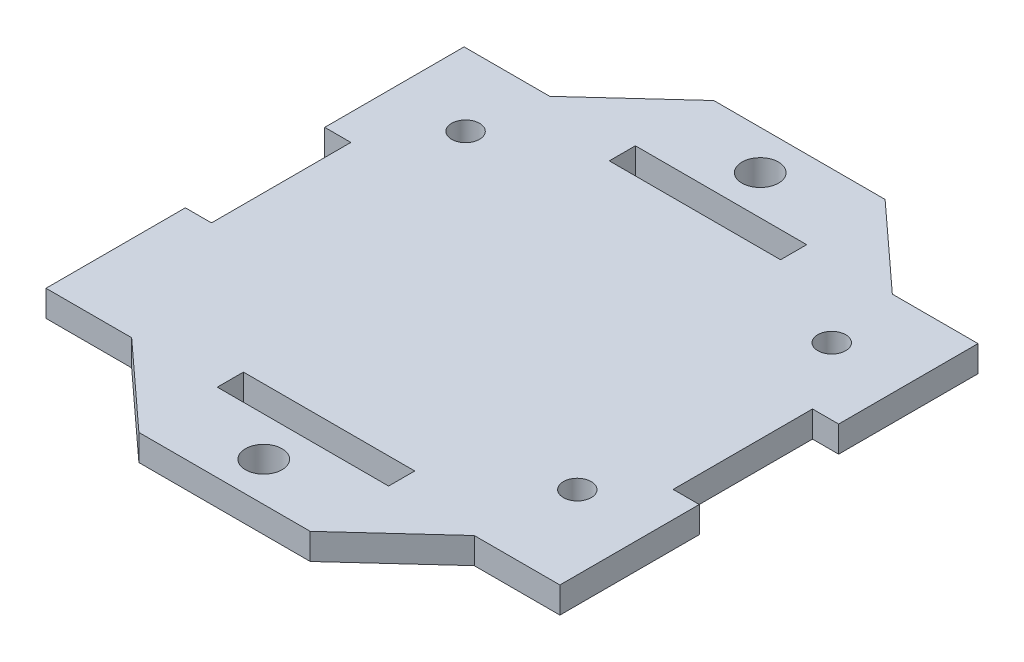
SolidWorks part; units mm, degrees
ref_plane "Front Plane" through (0, 0, 0) normal (0, 0, 1) x (1, 0, 0)
ref_plane "Top Plane" through (0, 0, 0) normal (0, 1, 0) x (1, 0, 0)
ref_plane "Right Plane" through (0, 0, 0) normal (1, 0, 0) x (0, 0, -1)
sketch "Sketch1" plane through (0, 0, 0) normal (0, 1, 0) x (1, 0, 0)
  line L0 (-29.5, 24) -> (-29.5, 8)
  line L1 (-25, -19.5) -> (25, -19.5) construction
  line L2 (-25, -19.5) -> (-25, 19.5) construction
  line L3 (-25, 19.5) -> (25, 19.5) construction
  line L4 (25, -19.5) -> (25, 19.5) construction
  line L5 (-25, -19.5) -> (25, 19.5) construction
  line L6 (-25, 19.5) -> (25, -19.5) construction
  line L11 (-29.5, 8) -> (-26.5, 8)
  line L12 (-26.5, 8) -> (-26.5, -8)
  line L13 (-26.5, -8) -> (-29.5, -8)
  line L14 (-29.5, -8) -> (-29.5, -24)
  line L15 (-29.5, -24) -> (-9.8333, -24)
  line L16 (-9.8333, -24) -> (-9.8333, -21)
  line L17 (-9.8333, -21) -> (9.8333, -21)
  line L18 (9.8333, -21) -> (9.8333, -24)
  line L19 (9.8333, -24) -> (29.5, -24)
  line L20 (-21.0185, 15.69) -> (0, 0) construction
  line L21 (29.5, -24) -> (29.5, -8)
  line L22 (29.5, -8) -> (26.5, -8)
  line L23 (26.5, -8) -> (26.5, 8)
  line L24 (26.5, 8) -> (29.5, 8)
  line L25 (29.5, 8) -> (29.5, 24)
  line L26 (29.5, 24) -> (9.8333, 24)
  line L27 (9.8333, 24) -> (9.8333, 21)
  line L28 (9.8333, 21) -> (-9.8333, 21)
  line L29 (-9.8333, 21) -> (-9.8333, 24)
  line L30 (-9.8333, 24) -> (-29.5, 24)
  line L31 (0, 0) -> (21.0185, 15.69) construction
  circle A0 centre (-21.0185, 15.69) radius 1.6
  circle A1 centre (21.0185, 15.69) radius 1.6
  circle A2 centre (21.0185, -13.52) radius 1.6
  point P0 (0, 0)
  point P6 (0, 0)
  point P23 (-26.5, 0)
  point P26 (0, -21)
  point P36 (0, 0)
  dimension "D8" = 3.2
  dimension "D1" = 50
  dimension "D2" = 39
  dimension "D3" = 3
  dimension "D4" = 4.5
  dimension "D5" = 4.5
  dimension "D7" = 42.037
  dimension "D9" = 3.81
  dimension "D10" = 29.21
  dimension "D6" = 2
extrude "Boss-Extrude1" add sketch "Sketch1" along normal blind 3
sketch "Sketch2" plane through (0, 3, 0) normal (0, 1, 0) x (1, 0, 0)
  line L0 (-19.6667, 24) -> (-9.8333, 33)
  line L1 (-9.8333, 24) -> (-29.5, 24) construction
  line L2 (-9.8333, 33) -> (9.8333, 33)
  line L3 (9.8333, 33) -> (19.6667, 24)
  line L4 (29.5, 24) -> (9.8333, 24) construction
  line L6 (-19.6667, 24) -> (19.6667, 24)
  line L7 (-9.8333, 24) -> (9.8333, 33) construction
  circle A0 centre (0, 28.5) radius 2.1
  point P13 (19.6667, 24)
  point P14 (0, 0)
  point P15 (-5.0041, 29.9151)
  point P16 (0, 28.5)
  dimension "D1" = 4.2
  dimension "D2" = 9
extrude "Boss-Extrude2" add sketch "Sketch2" against normal blind 3
mirror "Mirror1" about plane through (0, 0, 0) normal (0, 0, 1) of "Boss-Extrude2"
